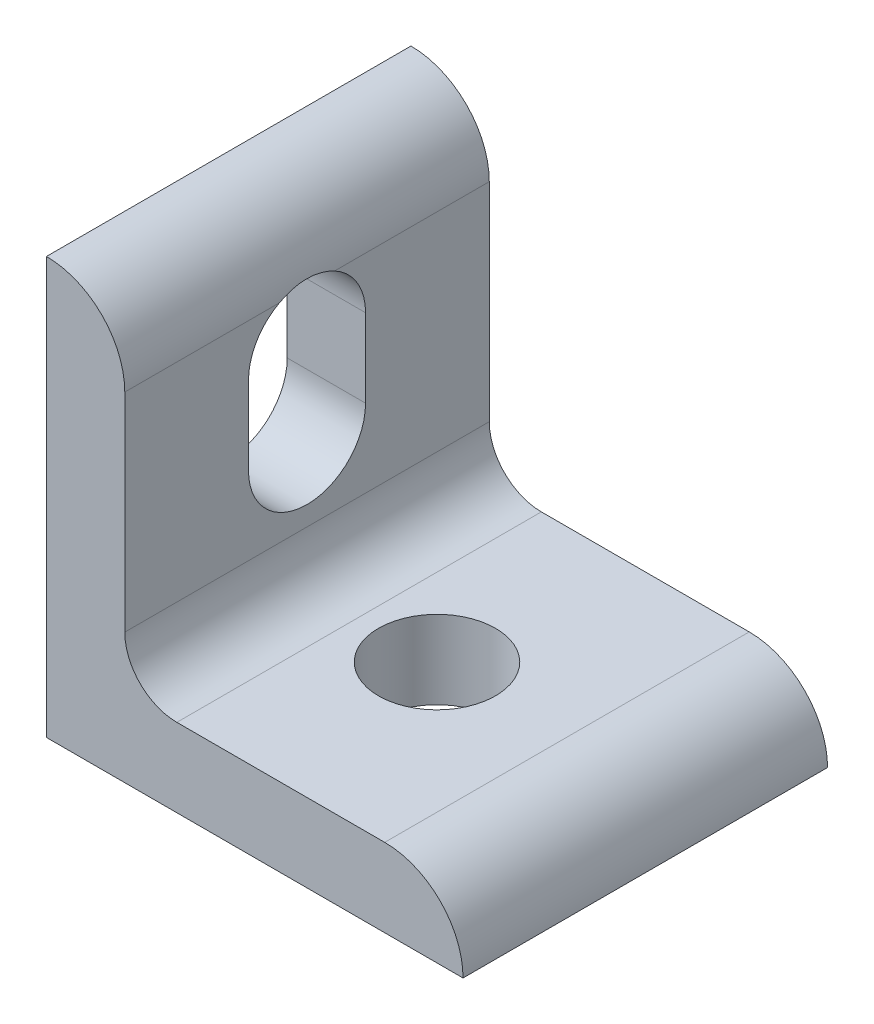
SolidWorks part; units mm, degrees
material "6061 Alloy"
ref_plane "Front Plane" through (0, 0, 0) normal (0, 0, 1) x (1, 0, 0)
ref_plane "Top Plane" through (0, 0, 0) normal (0, 1, 0) x (1, 0, 0)
ref_plane "Right Plane" through (0, 0, 0) normal (1, 0, 0) x (0, 0, -1)
sketch "Sketch1" plane through (0, 0, 0) normal (0, 0, 1) x (1, 0, 0)
  line L0 (12.7, -12.7) -> (-12.7, -12.7) construction
  line L1 (12.7, -12.7) -> (12.7, -7.9248) construction
  line L2 (-12.7, -12.7) -> (-12.7, 12.7) construction
  point P0 (-12.7, 0)
  point P3 (0, -12.7)
  dimension "Length" = 25.4
  dimension "Thickness" = 4.7752
sketch "Sketch2" plane through (0, 0, 0) normal (1, 0, 0) x (0, 0, -1)
  line L0 (-11.1125, -12.7) -> (11.1125, -12.7) construction
  line L2 (0, 4.7752) -> (0, 0) construction
  line L3 (0, -12.7) -> (0, 12.7) construction
  line L4 (3.5687, 4.7752) -> (-3.5687, 4.7752) construction
  point P4 (0, -12.7)
  point P12 (0, 4.7752)
  dimension "Width" = 22.225
  dimension "Bottom to Slot" = 12.7
  dimension "Slot Width" = 4.7752
  dimension "Slot Dia" = 7.1374
sketch "Sketch3" plane through (0, 0, 0) normal (0, 1, 0) x (1, 0, 0)
  line L0 (-3.5687, 0) -> (3.5687, 0) construction
  line L1 (12.7, 0) -> (-12.7, 0) construction
  point P5 (0, 0)
  dimension "Hole Dia" = 7.1374
sketch "Sketch4" plane through (0, 0, 0) normal (0, 0, 1) x (1, 0, 0)
  line L0 (-12.7, 12.7) -> (-12.7, -12.7)
  line L1 (-12.7, -12.7) -> (12.7, -12.7)
  line L2 (7.9248, -7.9248) -> (-4.7498, -7.9248)
  line L3 (-7.9248, -4.7498) -> (-7.9248, 7.9248)
  arc A0 (-4.7498, -7.9248) -> (-7.9248, -4.7498) centre (-4.7498, -4.7498) cw
  arc A1 (7.9248, -7.9248) -> (12.7, -12.7) centre (7.9248, -12.7) cw
  arc A2 (-7.9248, 7.9248) -> (-12.7, 12.7) centre (-12.7, 7.9248) ccw
  dimension "D1" = 3.175
extrude "Boss-Extrude1" add sketch "Sketch4" against normal up to vertex (11.1125 mm away) and the other way up to vertex (11.1125 mm away) up to point (0, -12.7, -11.1125) other way up to point (0, -12.7, 11.1125)
sketch "Sketch5" plane through (-7.9248, 0, 0) normal (1, 0, 0) x (0, 0, -1)
  line L0 (0, 4.7752) -> (0, 0) construction
  line L1 (3.5687, 4.7752) -> (-3.5687, 4.7752) construction
  line L2 (3.5687, 4.7752) -> (3.5687, 0)
  line L3 (-3.5687, 4.7752) -> (-3.5687, 0)
  arc A0 (3.5687, 4.7752) -> (-3.5687, 4.7752) centre (0, 4.7752) ccw
  arc A1 (-3.5687, 0) -> (3.5687, 0) centre (0, 0) ccw
  point P5 (0, 2.3876)
extrude "Cut-Extrude1" cut sketch "Sketch5" against normal through all both and the other way through all
sketch "Sketch6" plane through (0, -7.9248, 0) normal (0, 1, 0) x (1, 0, 0)
  line L0 (12.7, 0) -> (-12.7, 0) construction
  circle A0 centre (0, 0) radius 3.5687
extrude "Cut-Extrude2" cut sketch "Sketch6" against normal through all
ref_plane "Plane1" through (0, 0, 0) normal (0, 0, 1) x (1, 0, 0)
